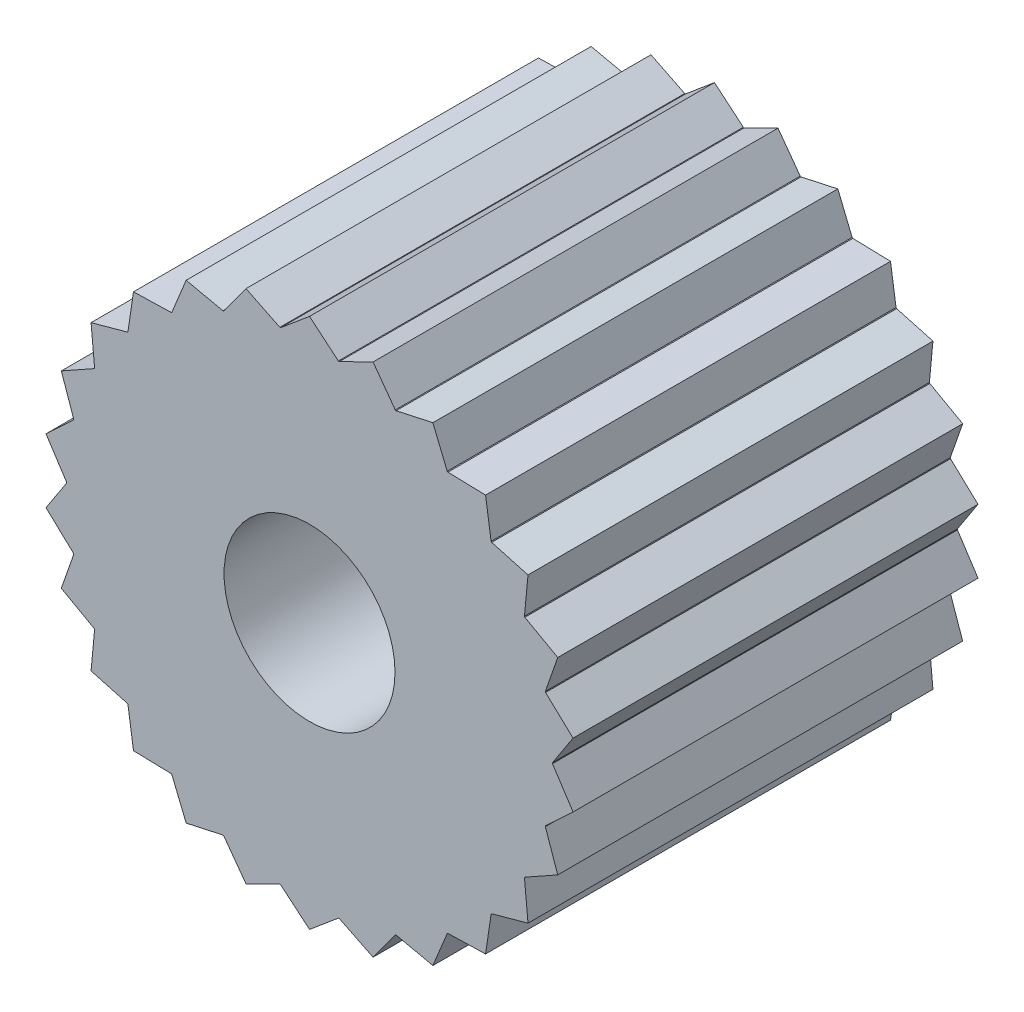
SolidWorks part; units mm, degrees
ref_plane "Alzado" through (0, 0, 0) normal (0, 0, 1) x (1, 0, 0)
ref_plane "Planta" through (0, 0, 0) normal (0, 1, 0) x (1, 0, 0)
ref_plane "Vista lateral" through (0, 0, 0) normal (1, 0, 0) x (0, 0, -1)
sketch "Croquis1" plane through (0, 0, 0) normal (0, 0, 1) x (1, 0, 0)
  circle A0 centre (0, 0) radius 1.9
  circle A1 centre (0, 0) radius 5.4
  dimension "D1" = 3.8
  dimension "D3" = 10.8
  dimension "D2" = 3.5
extrude "Saliente-Extruir1" add sketch "Croquis1" along normal mid plane 4.5
sketch "Croquis2" plane through (0, 0, -2.25) normal (0, 0, -1) x (-1, 0, 0)
  circle A0 centre (0, 0) radius 5.4 construction
  circle A1 centre (0, 0) radius 5.4
  circle A2 centre (0, 0) radius 4.1
  circle M3 centre (0, 0) radius 5.4
  circle M4 centre (0, 0) radius 1.9
  dimension "D1" = 1.3
extrude "Saliente-Extruir2" add sketch "Croquis2" along normal blind 4.5 contours A2 M4 | A2 M3 | M4 | A2 | A1 region at (5.2473, 0, -2.25) region at (3.984, 0, -2.25) region at (0, 0, -2.25)
sketch "Croquis6" plane through (0, 0, 0) normal (0, 0, 1) x (1, 0, 0)
  line L0 (0, -1.2864) -> (0, 7.503) construction
  line L1 (0, 5.4) -> (0, 5.9)
  line L2 (0, 5.9) -> (0.6414, 5.3618)
  line L3 (0, 5.9) -> (-0.6414, 5.3618)
  circle A0 centre (0, 0) radius 5.4 construction
  arc A1 (0.6414, 5.3618) -> (-0.6414, 5.3618) centre (0, 0) ccw
  dimension "D1" = 50
  dimension "D2" = 0.5
extrude "Saliente-Extruir3" add sketch "Croquis6" against normal through all and the other way through all contours A1 L2 L1 | A1 L1 L3 region at (-0.211, 5.5584, 0) region at (0.211, 5.5584, 0)
pattern_circular "MatrizC1" count 26 over 360 about axis through (0, 0, 2.25) along (0, 0, 1) of "Saliente-Extruir3"
hole_wizard "Taladro de margen para M31" positions "Croquis7" profile "Croquis8" hole size "M3" standard "Ansi Metric" end condition through all
sketch "Croquis7" plane through (0, 0, -2.25) normal (0, 0, 1) x (1, 0, 0)
  point P0 (0, 0)
sketch "Croquis8" plane through (0, 0, -2.25) normal (1, 0, 0) x (0, -1, 0)
  line L0 (0, 0) -> (0, 4.5)
  line L1 (0, 4.5) -> (1.9, 4.5)
  line L2 (1.9, 4.5) -> (1.9, 0)
  line L5 (1.9, 0) -> (0, 0)
  line L11 (0, -6.35) -> (0, 107.95) construction
  dimension "Diámetro de taladro hasta el siguiente" = 3.8
  dimension "Profundidad de taladro hasta el siguiente" = 4.5
